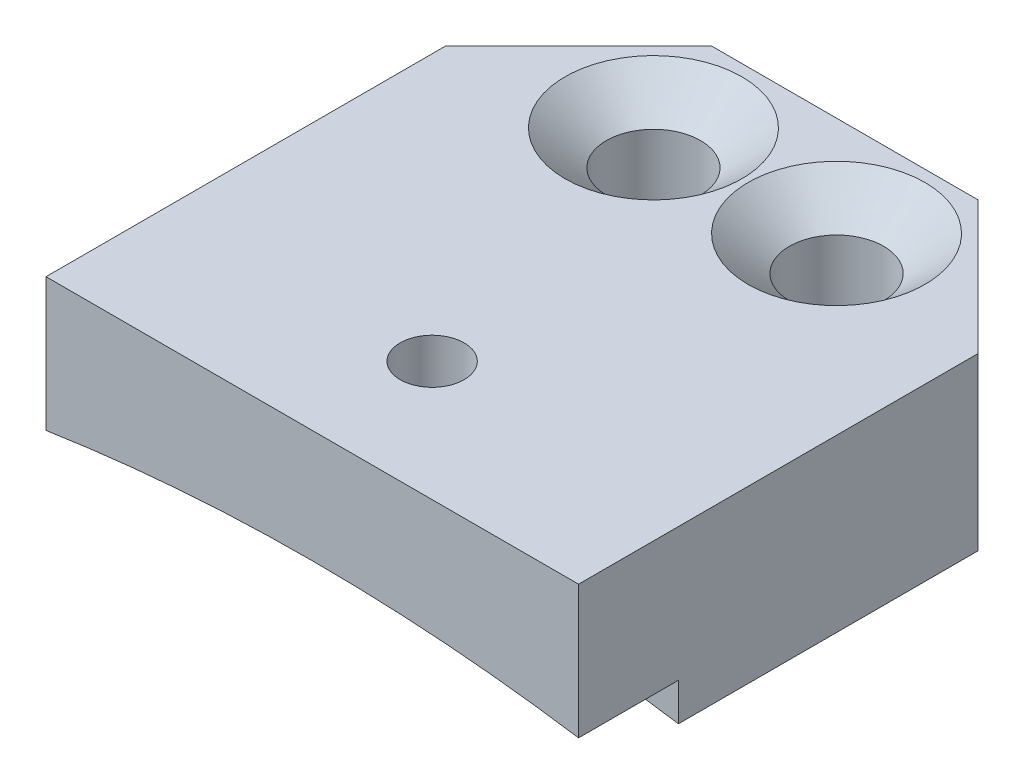
SolidWorks part; units mm, degrees
ref_plane "Front Plane" through (0, 0, 0) normal (0, 0, 1) x (1, 0, 0)
ref_plane "Top Plane" through (0, 0, 0) normal (0, 1, 0) x (1, 0, 0)
ref_plane "Right Plane" through (0, 0, 0) normal (1, 0, 0) x (0, 0, -1)
sketch "Sketch1" plane through (0, 0, 0) normal (0, 1, 0) x (1, 0, 0)
  line L0 (-28.5118, 6.4953) -> (-22.1618, 12.8453)
  line L1 (-22.1618, 12.8453) -> (-9.4618, 12.8453)
  line L2 (-28.5118, 6.4953) -> (-28.5118, -12.5547)
  line L3 (-28.5118, -12.5547) -> (-3.1118, -12.5547)
  line L4 (-3.1118, 6.4953) -> (-3.1118, -12.5547)
  line L5 (-9.4618, 12.8453) -> (-3.1118, 6.4953)
  line L6 (-15.8118, -12.5547) -> (-15.8118, 12.8453) construction
  line L8 (-3.1118, 6.4953) -> (-3.1118, 12.8453) construction
  line L9 (-3.1118, 12.8453) -> (-9.4618, 12.8453) construction
  dimension "D1" = 12.7
  dimension "D2" = 25.4
  dimension "D3" = 25.4
extrude "Boss-Extrude1" add sketch "Sketch1" along normal blind 6.35
sketch "Sketch2" plane through (0, 0, 12.5547) normal (0, 0, 1) x (1, 0, 0)
  circle A0 centre (-15.8118, -82.8523) radius 83.82
  dimension "D1" = 167.64
extrude "Cut-Extrude1" cut sketch "Sketch2" against normal through all both and the other way through all
sketch "Sketch5" plane through (0, 0, -12.8453) normal (0, 0, -1) x (-1, 0, 0)
  line L0 (3.1118, 6.35) -> (3.1118, 0) construction
  line L1 (3.1118, 6.35) -> (3.1118, 0)
  line L4 (28.5118, 6.35) -> (28.5118, 0) construction
  line L5 (28.5118, 6.35) -> (28.5118, 0)
  line L6 (28.5118, -1.7992) -> (28.5118, 0)
  line L7 (3.1118, -1.7992) -> (3.1118, 0)
  line L8 (3.1118, 6.35) -> (28.5118, 6.35)
  arc A0 (3.1118, -1.7992) -> (28.5118, -1.7992) centre (15.8118, -82.8523) cw
  arc A1 (28.5118, 0) -> (3.1118, 0) centre (15.8118, -82.8523) ccw construction
  arc A2 (28.5118, 0) -> (3.1118, 0) centre (15.8118, -82.8523) ccw construction
  dimension "D1" = 82.042
extrude "Boss-Extrude2" add sketch "Sketch5" against normal blind 20.6375
chamfer "Chamfer1" distance 6.35 angle 45 2 edges at (-28.5118, 2.2754, -12.8453) (-3.1118, 2.2754, -12.8453)
hole_wizard "CSK for #8 Flat Head Machine Screw (100)1" positions "Sketch3" profile "Sketch4" countersink size "#8" standard "ANSI Inch" end condition through all
sketch "Sketch3" plane through (0, 6.35, 0) normal (0, 1, 0) x (1, 0, 0)
  line L0 (-15.8118, 12.8453) -> (-15.8118, 3.4006) construction
  line L1 (-9.4618, 12.8453) -> (-22.1618, 12.8453) construction
  point P0 (-20.1775, 8.0828)
  point P12 (-11.4462, 8.0828)
  dimension "D1" = 4.7625
  dimension "D2" = 4.3656
sketch "Sketch4" plane through (-20.1775, 6.35, -8.0828) normal (1, 0, 0) x (0, 0, 1)
  line L0 (0, 0) -> (0, 8.1492)
  line L1 (0, 8.1492) -> (2.2479, 8.1492)
  line L2 (2.2479, 8.1492) -> (2.2479, 1.6518)
  line L3 (2.2479, 1.6518) -> (4.2164, 0)
  line L5 (4.2164, 0) -> (0, 0)
  line L6 (-2.2479, 1.6518) -> (-4.2164, 0) construction
  line L11 (0, -6.35) -> (0, 107.95) construction
  dimension "Thru Hole Dia." = 4.4958
  dimension "Thru Hole Depth" = 8.1492
  dimension "Near C'Sink Dia." = 8.4328
  dimension "Near C'Sink Angle" = 100
sketch "Sketch6" plane through (0, 6.35, 0) normal (0, 1, 0) x (1, 0, 0)
  circle A0 centre (-15.8102, -6.8397) radius 1.524 construction
  circle A1 centre (-15.8102, -6.8397) radius 1.524
extrude "Cut-Extrude2" cut sketch "Sketch6" against normal through all
